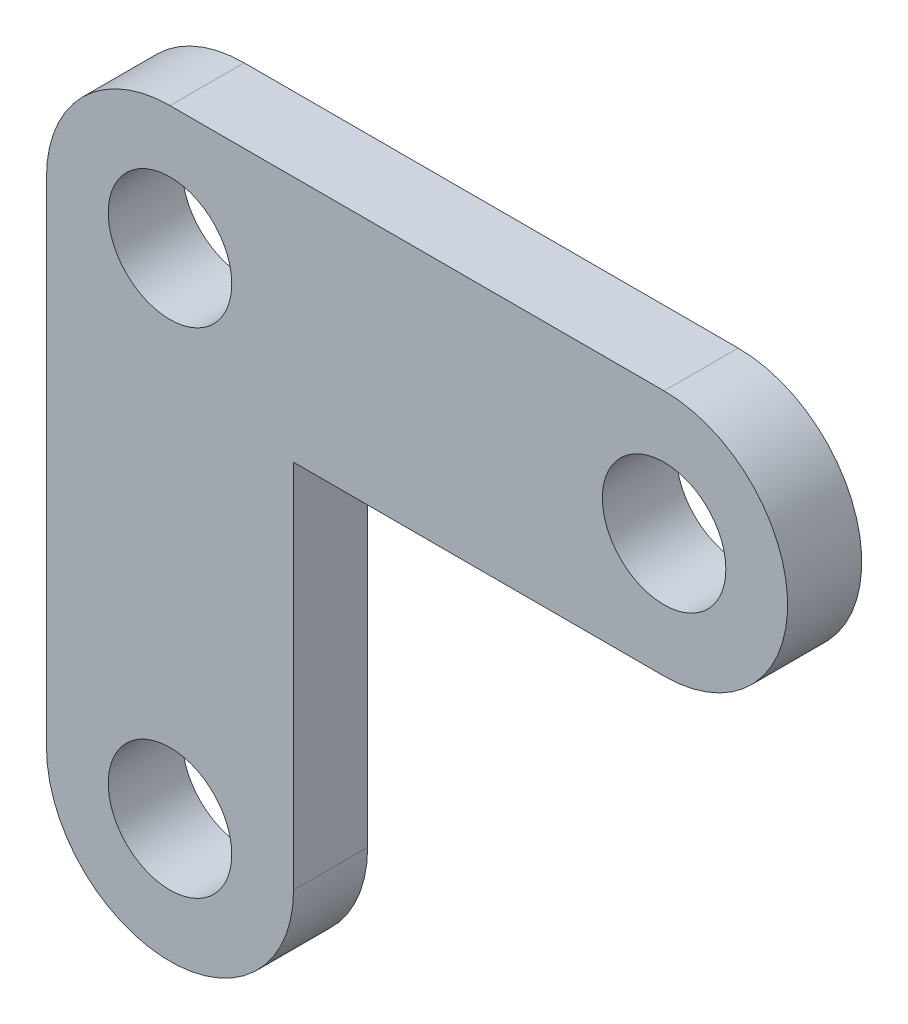
SolidWorks part; units mm, degrees
ref_plane "Front Plane" through (0, 0, 0) normal (0, 0, 1) x (1, 0, 0)
ref_plane "Top Plane" through (0, 0, 0) normal (0, 1, 0) x (1, 0, 0)
ref_plane "Right Plane" through (0, 0, 0) normal (1, 0, 0) x (0, 0, -1)
sketch "Sketch1" plane through (0, 0, 0) normal (0, 0, 1) x (1, 0, 0)
  line L2 (4.0012, 11.6661) -> (4.0012, 31.6661)
  line L3 (4.0012, 31.6661) -> (14.0012, 31.6661)
  line L4 (14.0012, 11.6661) -> (14.0012, 31.6661)
  line L5 (9.0012, 36.6661) -> (29.0012, 36.6661)
  line L6 (9.0012, 36.6661) -> (9.0012, 26.6661)
  line L7 (9.0012, 26.6661) -> (29.0012, 26.6661)
  arc A0 (4.0012, 11.6661) -> (14.0012, 11.6661) centre (9.0012, 11.6661) ccw
  circle A1 centre (9.0012, 11.6661) radius 2.5
  arc A2 (29.0012, 36.6661) -> (29.0012, 26.6661) centre (29.0012, 31.6661) cw
  circle A3 centre (29.0012, 31.6661) radius 2.5
  arc A4 (9.0012, 36.6661) -> (4.0012, 31.6661) centre (9.0012, 31.6661) ccw
  circle A5 centre (9.0012, 31.6661) radius 2.5
  point P20 (14.0012, 26.6661)
  point P27 (14.0012, 26.6661)
  dimension "D3" = 5
  dimension "D7" = 5
  dimension "D9" = 5
  dimension "D1" = 20
  dimension "D2" = 10
  dimension "D4" = 15
  dimension "D5" = 20
  dimension "D6" = 10
  dimension "D8" = 15
extrude "Boss-Extrude1" add sketch "Sketch1" along normal blind 3 contours A5 L3 L4 L7 A2 L5 L6 A3 | A5 L3 L2 A0 L4 L7 L6 A1 | A5 L6 L7 L4 L3 | A5 L6 A4 L3 region at (8.6992, 18.9724, 0) region at (6.5254, 34.1419, 0) region at (21.6949, 31.9681, 0) region at (11.8528, 28.8146, 0)
